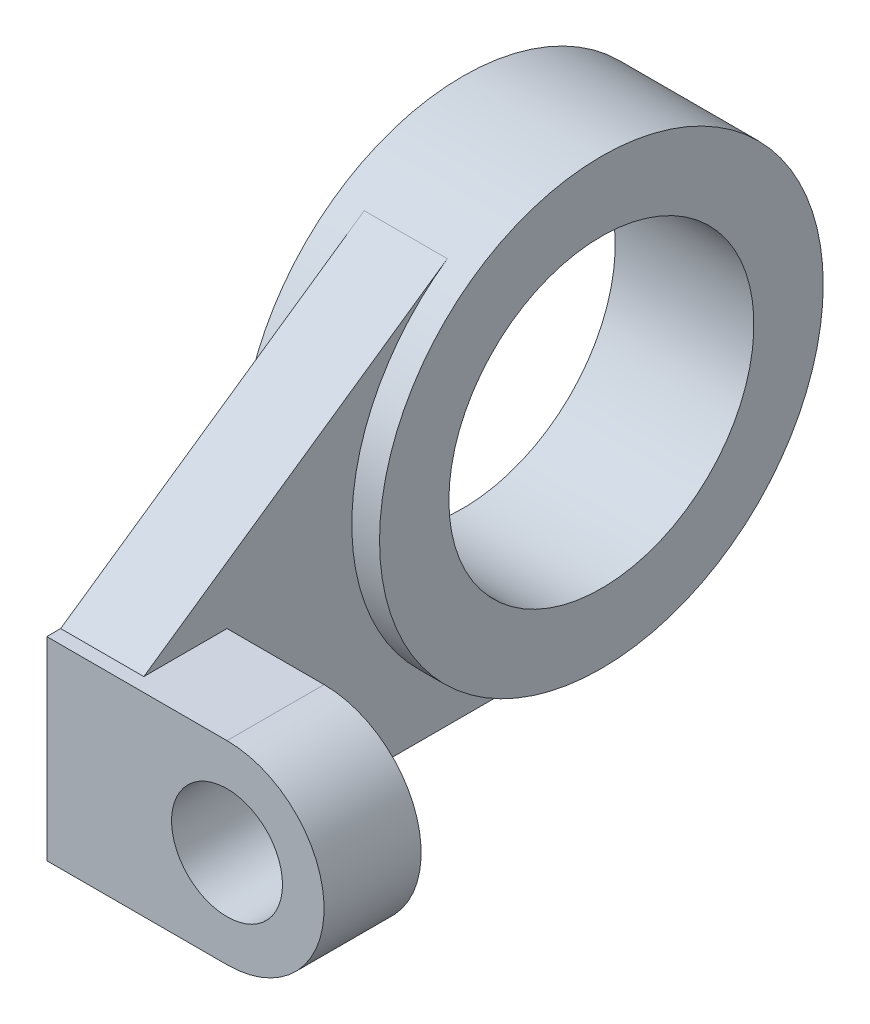
SolidWorks part; units mm, degrees
note: The reader was unsure of these and kept them because the rebuilt part matched: shared geometry of "Sketch1<3>".
ref_plane "Front Plane" through (0, 0, 0) normal (0, 0, 1) x (1, 0, 0)
ref_plane "Top Plane" through (0, 0, 0) normal (0, 1, 0) x (1, 0, 0)
ref_plane "Right Plane" through (0, 0, 0) normal (1, 0, 0) x (0, 0, -1)
sketch "Sketch1" plane through (0, 0, 0) normal (1, 0, 0) x (0, 0, -1)
  line L0 (0, -50.8) -> (-101.6, -50.8)
  line L1 (-101.6, -50.8) -> (-101.6, -6.35)
  line L2 (-101.6, -6.35) -> (-98.425, -6.35)
  line L3 (-98.425, -6.35) -> (-28.9141, 41.7686)
  circle A0 centre (0, 0) radius 34.925
  circle A1 centre (0, 0) radius 50.8
  dimension "D1" = 69.85
  dimension "D2" = 101.6
  dimension "D3" = 101.6
  dimension "D4" = 44.45
  dimension "D5" = 3.175
extrude "Boss-Extrude1" add sketch "Sketch1" along normal mid plane 19.05 contours A1 A0 | A1 L3 L2 L1 L0
extrude "Boss-Extrude2" add sketch "Sketch1<3>" along normal mid plane 31.75 contours A1 A0
sketch "Sketch1<3>" plane through (0, 0, 0) normal (1, 0, 0) x (0, 0, -1) same geometry as "Sketch1"
sketch "Sketch2" plane through (9.525, 0, 0) normal (1, 0, 0) x (0, 0, -1)
  line L1 (-101.6, -50.8) -> (-79.375, -50.8)
  line L2 (-101.6, -50.8) -> (-101.6, -6.35)
  line L3 (-101.6, -6.35) -> (-79.375, -6.35)
  line L4 (-79.375, -50.8) -> (-79.375, -6.35)
  dimension "D1" = 22.225
extrude "Boss-Extrude3" add sketch "Sketch2" along normal blind 50.8
sketch "Sketch3" plane through (0, 0, 101.6) normal (0, 0, 1) x (1, 0, 0)
  line L0 (60.325, -28.575) -> (35.2367, -28.575) construction
  line L1 (60.325, -6.35) -> (60.325, -50.8) construction
  line L2 (-9.525, 41.7686) -> (-9.525, -50.8) construction
  line L3 (31.75, -6.35) -> (60.325, -6.35)
  line L4 (60.325, -6.35) -> (60.325, -50.8)
  line L5 (60.325, -50.8) -> (31.75, -50.8)
  circle A0 centre (31.75, -28.575) radius 12.7
  circle A1 centre (31.75, -28.575) radius 22.225
  dimension "D2" = 25.4
  dimension "D3" = 44.45
  dimension "D1" = 41.275
extrude "Cut-Extrude1" cut sketch "Sketch3" against normal through all
